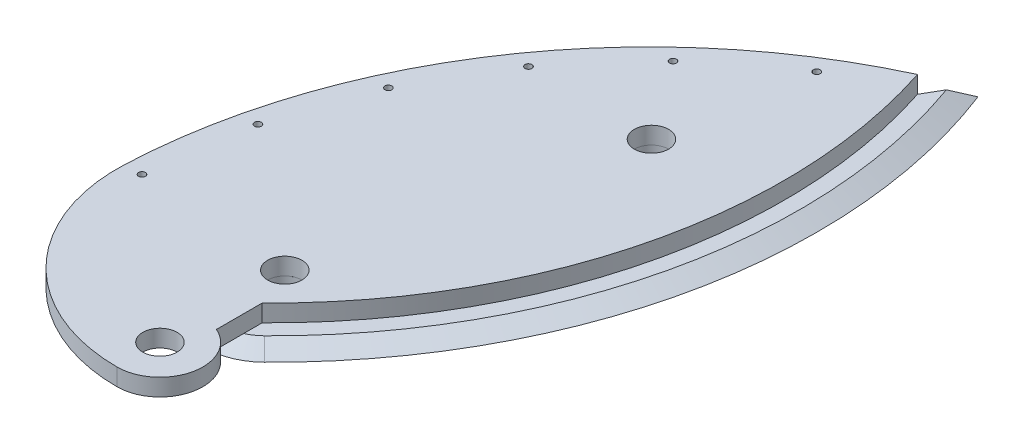
SolidWorks part; units mm, degrees
ref_plane "Ön Düzlem" through (0, 0, 0) normal (0, 0, 1) x (1, 0, 0)
ref_plane "Üst Düzlem" through (0, 0, 0) normal (0, 1, 0) x (1, 0, 0)
ref_plane "Sağ Düzlem" through (0, 0, 0) normal (1, 0, 0) x (0, 0, -1)
sketch "Çizim1" plane through (0, 0, 0) normal (0, 1, 0) x (1, 0, 0)
  line L0 (0, 87.5) -> (50, 174.1025) construction
  line L1 (5, 24.791) -> (5, 11.4564)
  line L2 (0, 0) -> (0, 87.5) construction
  circle A0 centre (0, 0) radius 50 construction
  circle A1 centre (0, 87.5) radius 100 construction
  circle A2 centre (0, 0) radius 12.5
  circle A3 centre (0, 0) radius 5
  arc A4 (50, 174.1025) -> (0, 12.5) centre (-99.0854, 131.6934) cw construction
  arc A6 (42.7893, 177.883) -> (5, 24.791) centre (-99.0854, 131.6934) cw
  circle A7 centre (0, 36.3607) radius 5
  circle A8 centre (20.3782, 122.796) radius 5
  circle A9 centre (0, 36.3607) radius 17.5 construction
  arc A10 (42.7893, 177.883) -> (-49.9511, 39.7117) centre (109.8923, 32.6343) ccw
  arc A12 (-49.9511, 39.7117) -> (0, -12.5) centre (0, 37.5) ccw
  point P11 (0, 0)
  point P24 (-79.1197, 30.6733)
  point P25 (0, 0)
  point P26 (-14.0444, 36.2804)
  point P27 (0, 0)
  dimension "D1" = 100
  dimension "D2" = 200
  dimension "D3" = 25
  dimension "D4" = 10
  dimension "D6" = 155
  dimension "D8" = 10
  dimension "D9" = 35
  dimension "D10" = 160
  dimension "D11" = 50
  dimension "D5" = 150
  dimension "D7" = 5
  dimension "D12" = 13.3346
extrude "Yükseklik-Ekstrüzyon1" add sketch "Çizim1" along normal blind 5 contours A6 A2 L1 A8 A7 | A2 A3 region at (0.6077, 0, -83.6883) region at (10.1624, 0, -6.6529)
sketch "Çizim2" plane through (0, 0, 0) normal (0, -1, 0) x (1, 0, 0)
  line L1 (49.2396, -189.0553) -> (-17.5, -73.4589)
  line L3 (-17.5, -30.6342) -> (-17.5, -73.4589)
  line L4 (0, 0) -> (0, -87.5) construction
  line L6 (0, -87.5) -> (50, -174.1025) construction
  arc A0 (12.2517, -18.1384) -> (49.2396, -189.0553) centre (-99.0854, -131.6934) cw
  arc A1 (50, -174.1025) -> (0, -12.5) centre (-99.0854, -131.6934) ccw construction
  circle A3 centre (0, -30.6342) radius 17.5
  circle A4 centre (0, -36.3607) radius 5
  circle A5 centre (0, -36.3607) radius 5 construction
  circle M4 centre (20.3782, -122.796) radius 5
  circle M5 centre (0, -36.3607) radius 5
  arc M6 (42.7893, -177.883) -> (5, -24.791) centre (-99.0854, -131.6934) ccw
  line M7 (5, -24.791) -> (5, -11.4564)
  dimension "D1" = 35
extrude "blade" add sketch "Çizim2" along normal blind 3 separate body contours A3 M7 M6 M5 | A3 L3 L1 M6 M4 | A3 L1 A0 M6 | A3 M6 M7 region at (47.5512, 0, -182.5819) region at (20.2319, 0, -96.3034) region at (11.2233, 0, -24.6559) region at (-2.4868, 0, -31.337)
chamfer "Pah1" distance 3 angle 60 3 edges at (-17.5, 0, -52.0465) (-6.7766, 0, -14.4995) (56.3471, 0, -98.0565) first distance on face at (-17.5, -1.5, -52.0465) first distance on face at (-4.7004, -1.5, -19.4429) first distance on face at (43.5464, -1.5, -100.8267)
sketch "Çizim3" plane through (0, 5, 0) normal (0, 1, 0) x (1, 0, 0)
  line L0 (42.7893, 172.3561) -> (109.8923, 32.6343) construction
  line L1 (109.8923, 32.6343) -> (-44.946, 39.7117) construction
  arc A0 (42.7893, 172.3561) -> (-44.946, 39.7117) centre (109.8923, 32.6343) ccw construction
  arc A1 (42.7893, 177.883) -> (-49.9511, 39.7117) centre (109.8923, 32.6343) ccw construction
  circle A2 centre (27.4308, 163.8787) radius 1
  circle A3 centre (3.8079, 145.6436) radius 1
  circle A4 centre (-15.8826, 123.2194) radius 1
  circle A5 centre (-30.9109, 97.4374) radius 1
  circle A6 centre (-40.7199, 69.2532) radius 1
  circle A7 centre (-44.946, 39.7117) radius 1
  point P23 (109.8923, 32.6343)
  dimension "D1" = 5
  dimension "D3" = 2
  dimension "D2" = 6
extrude "kanca delikleri" cut sketch "Çizim3" against normal through all
